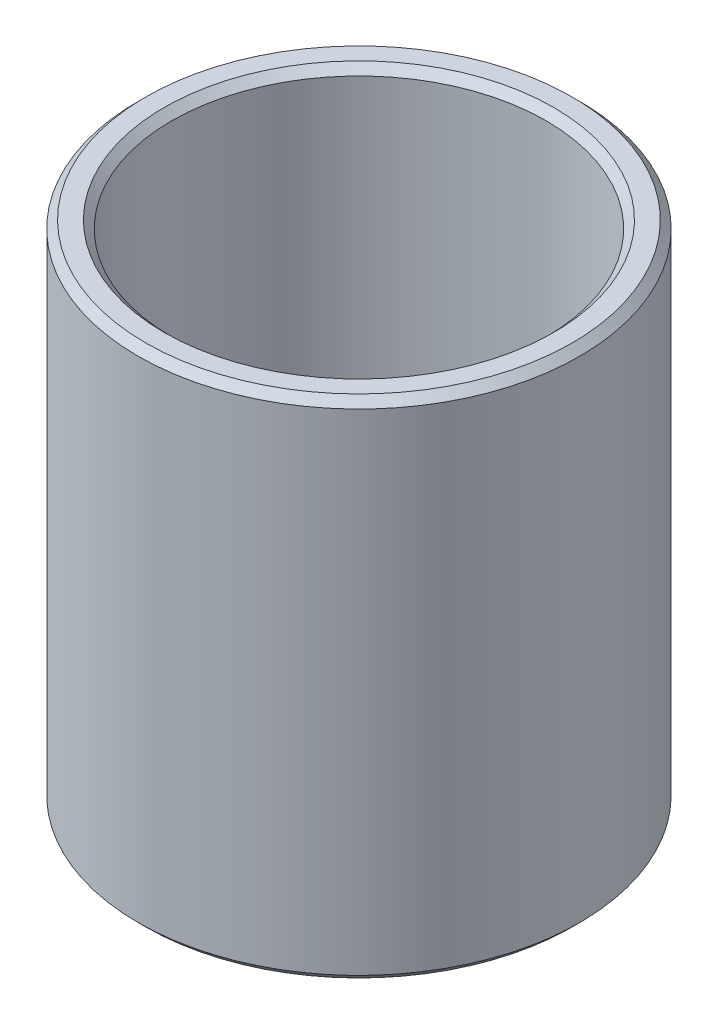
SolidWorks part; units mm, degrees
ref_plane "Front Plane" through (0, 0, 0) normal (0, 0, 1) x (1, 0, 0)
ref_plane "Top Plane" through (0, 0, 0) normal (0, 1, 0) x (1, 0, 0)
ref_plane "Right Plane" through (0, 0, 0) normal (1, 0, 0) x (0, 0, -1)
sketch "Sketch1" plane through (0, 0, 0) normal (0, 1, 0) x (1, 0, 0)
  circle A0 centre (0, 0) radius 20
  dimension "SLEEVE_OD" = 40
extrude "Boss-Extrude1" add sketch "Sketch1" along normal blind 45.8152
sketch "Sketch2" plane through (0, 0, 0) normal (0, 1, 0) x (1, 0, 0)
  circle A0 centre (0, 0) radius 16.9551
  dimension "BORE_D" = 33.9103
extrude "Cut-Extrude1" cut sketch "Sketch2" along normal through all
chamfer "Chamfer1" distance 0.694 angle 45 4 edges at (0, 45.8152, 16.9551) (0, 0, 16.9551) (0, 0, 20) (0, 45.8152, 20)
